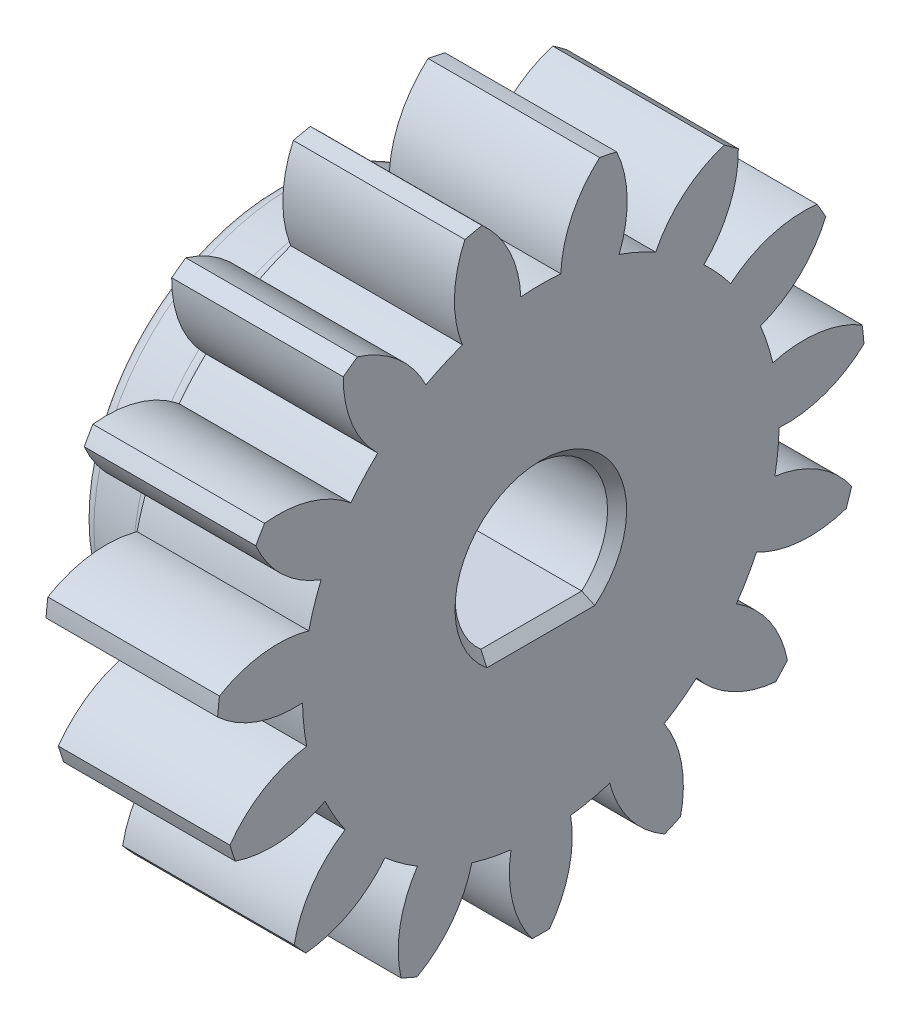
SolidWorks part; units mm, degrees
ref_plane "Plane1" through (0, 0, 0) normal (0, 0, 1) x (1, 0, 0)
ref_plane "Plane2" through (0, 0, 0) normal (0, 1, 0) x (1, 0, 0)
ref_plane "Plane3" through (0, 0, 0) normal (1, 0, 0) x (0, 0, -1)
sketch "HoldingSke" plane through (0, 0, 0) normal (0, 1, 0) x (1, 0, 0)
  line L0 (0, 0) -> (0.483, -0.1294)
  line L1 (-15, 0) -> (100, 0) construction
  line L2 (0, 0) -> (-2.1039, 2.3779)
  line L3 (0, 0) -> (-11.863, 4.5341)
  line L4 (0, 0) -> (8.3417, 2.2352)
  line L5 (0, 0) -> (-13.1173, -4.8924)
  line L6 (0, 0) -> (-7.4607, -5.0337)
  line L7 (-2.1039, 2.3779) -> (0.9096, 16.0498)
  line L8 (-76.2, 54.61) -> (-74.8, 54.61)
  line L9 (-71.009, 38.7566) -> (-53.1078, 45.2721)
  line L10 (-76.2, 71.12) -> (104.1128, 71.12)
  line L11 (0, 0) -> (-9, 0)
  line L12 (-76.2, 101.6) -> (-76.133, 101.6)
  line L13 (24.9733, 27.94) -> (52.9518, 28.4284)
  line L14 (24.9733, 27.94) -> (24.9743, 27.94)
  line L15 (24.9733, 27.94) -> (100.4006, 29.5858)
  line L16 (-63.627, -2) -> (-12.827, -2)
  circle A0 centre (0, 0) radius 4
  circle A1 centre (0, 0) radius 11
  circle A2 centre (0, 0) radius 11
  circle A3 centre (0, 0) radius 4
  dimension "Num_teeth" = 15
  dimension "Pitch_radius" = 180.3128
  dimension "Width" = 9
  dimension "Thickness" = 9
sketch "BasProSke" plane through (0, 0, 0) normal (0, 1, 0) x (1, 0, 0)
  line L0 (-10, 0) -> (60, 0) construction
  line L1 (0, 0) -> (0, 17)
  line L2 (0, 0) -> (9, 0)
  line L3 (9, 0) -> (9, 17)
  line L4 (9, 17) -> (0, 17)
  dimension "Thickness" = 9
  dimension "Diameter" = 34
revolve "Base-Revolve" add sketch "BasProSke" angle 360 about L0
sketch "TooCutSke" plane through (0, 0, 0) normal (1, 0, 0) x (0, 0, -1)
  line L1 (0, 0) -> (0, 107) construction
  line L2 (0, 0) -> (-1.6851, 14.905) construction
  line L3 (0, 0) -> (-6.2081, 29.2069) construction
  line L4 (-1.6851, 14.905) -> (-3.1041, 14.6034) construction
  arc A0 (1.0501, 12.4548) -> (-1.0501, 12.4548) centre (0, 0) ccw
  arc A1 (3.1109, 16.7388) -> (-3.1109, 16.7388) centre (0, 0) ccw
  circle A2 centre (0, 0) radius 15 construction
  circle A3 centre (0, 0) radius 14.0954 construction
  arc A4 (-1.0501, 12.4548) -> (-3.1109, 16.7388) centre (-7.045, 12.2085) ccw
  arc A5 (3.1109, 16.7388) -> (1.0501, 12.4548) centre (7.045, 12.2085) ccw
extrude "ToothCut" cut sketch "TooCutSke" along normal through all
fillet "Breaks" [suppressed] radius 0.04
fillet "RootFillets" [suppressed] radius 0.501
pattern_circular "TeethCuts" count 15 every 24 about axis through (-10, 0, 0) along (1, 0, 0) of "ToothCut", "RootFillets", "Breaks"
sketch "HubNeaOneSke" plane through (0, 0, 0) normal (-1, 0, 0) x (0, 0, 1)
  circle A0 centre (0, 0) radius 11
  dimension "Diameter" = 22
extrude "HubNearOne" add sketch "HubNeaOneSke" along normal blind 5.0001
sketch "HubNeaBotSke" plane through (0, 0, 0) normal (-1, 0, 0) x (0, 0, 1)
  circle A0 centre (0, 0) radius 11
  dimension "Diameter" = 22
extrude "HubNearBoth" [suppressed] add sketch "HubNeaBotSke" along normal blind 2.5
ref_plane "FarPln" through (9, 0, 0) normal (1, 0, 0) x (0, 0, -1)
sketch "HubFarSke" plane through (9, 0, 0) normal (1, 0, 0) x (0, 0, -1)
  circle A0 centre (0, 0) radius 11
  dimension "Diameter" = 22
extrude "HubFar" [suppressed] add sketch "HubFarSke" along normal blind 2.5
sketch "BorSke" plane through (0, 0, 0) normal (1, 0, 0) x (0, 0, -1)
  circle A0 centre (0, 0) radius 4
  dimension "Diameter" = 8
extrude "Bore" cut sketch "BorSke" along normal mid plane 28.0001
sketch "KeySke" plane through (0, 0, 0) normal (1, 0, 0) x (0, 0, -1)
  line L0 (-1.5, 0) -> (-1.5, 5.4)
  line L1 (-1.5, 5.4) -> (1.5, 5.4)
  line L2 (1.5, 5.4) -> (1.5, 0)
  line L3 (0, 0) -> (0, 34) construction
  line L4 (-1.5, 0) -> (1.5, 0)
  dimension "Width" = 3
extrude "Keyway" [suppressed] cut sketch "KeySke" along normal mid plane 28.0001
pattern_circular "Keyway2" [suppressed] count 2 every 90 about axis through (-10, 0, 0) along (1, 0, 0)
sketch "Szkic1" plane through (0, 0, 0) normal (1, 0, 0) x (0, 0, -1)
  line L0 (-4.7612, 4) -> (4.8559, 4) construction
  line L1 (-2.6458, -3) -> (2.6458, -3)
  line L2 (-2.6458, -3) -> (-2.6458, -4)
  line L3 (-2.6458, -4) -> (2.6458, -4)
  line L4 (2.6458, -3) -> (2.6458, -4)
  circle A0 centre (0, 0) radius 4 construction
  dimension "D1" = 7
extrude "Dodanie-wyciągnięcie1" add sketch "Szkic1" along normal through all and the other way through all
draft "Pochylenie1" type of draft neutral plane draft angle 10 faces to draft 1 face at (-5.0001, 0, 11) neutral plane through (0, 0, 0) neutral plane normal (-1, 0, 0) parameters "D1"=10
fillet "Zaokrąglenie1" radius 2 1 edges at (0, 0, -11)
fillet "Zaokrąglenie2" radius 1 1 edges at (-5.0001, 0, 10.1184)
chamfer "Sfazowanie1" distance 0.5 angle 45 4 edges at (-5.0001, 4, 0) (-5.0001, -3, 0) (9, -3, 0) (9, 4, 0)
equation "' \"Module@HoldingSke\" = 6.35"
equation "' \"Num_teeth@HoldingSke\" = 12"
equation "' \"Ap@HoldingSke\" =  20"
equation "' \"Ap@HoldingSke\" = 20"
equation "' \"Width@HoldingSke\" = 0.5 * 25.4"
equation "' \"Hub_dia@HoldingSke\"= 1 * 25.4"
equation "' \"Hub_dia@HoldingSke\" = 1 * 25.4"
equation "' \"Overall_len@HoldingSke\" = 1.0 * 25.4"
equation "' \"Bore@HoldingSke\" = 0.75 * 25.4"
equation "' \"T_dim@HoldingSke\" = 0.1 * 25.4"
equation "' \"Width@KeySke\" = 0.25 * 25.4"
equation "' \"Show_teeth@HoldingSke\" = 13"
equation "' \"Backlash@HoldingSke\" = 0.009 * 25.4"
equation "' \"Addendum_fac@HoldingSke\" = 1.0"
equation "' \"Dedendum_fac@HoldingSke\" = 1.25"
equation "' \"Dedendum_add@HoldingSke\" = 0.00005 * 25.4"
equation "' \"Clearance_fac@HoldingSke\" = 0.25"
equation "\"Pitch@HoldingSke\" = 1 / \"Module@HoldingSke\""
equation "\"Overcut_dia@TooCutSke\" = (\"Num_teeth@HoldingSke\" + 2 * \"Addendum_fac@HoldingSke\") / \"Pitch@HoldingSke\" + 0.002 * 25.4"
equation "\"Pitch_dia@TooCutSke\" = \"Num_teeth@HoldingSke\" / \"Pitch@HoldingSke\""
equation "\"Base_dia@TooCutSke\" = \"Num_teeth@HoldingSke\" / \"Pitch@HoldingSke\" * cos((\"Ap@HoldingSke\"  * 3.14159265 / 180))"
equation "\"Root_dia@TooCutSke\" = (\"Num_teeth@HoldingSke\" + 2) / \"Pitch@HoldingSke\" - 2 * (\"Addendum_fac@HoldingSke\" + \"Dedendum_fac@HoldingSke\") / \"Pitch@HoldingSke\" - \"Dedendum_add@HoldingSke\" * 2"
equation "\"Half_ang@TooCutSke\" = 180 / \"Num_teeth@HoldingSke\""
equation "\"Half_CT@TooCutSke\" = \"Num_teeth@HoldingSke\" / \"Pitch@HoldingSke\" * sin((3.14159265 / 2 / \"Num_teeth@HoldingSke\")) / 2 - 7 * \"Backlash@HoldingSke\" / 4"
equation "\"Flank_rad@TooCutSke\" = \"Num_teeth@HoldingSke\" / \"Pitch@HoldingSke\" / 5"
equation "\"Radius@RootFillets\" = \"Clearance_fac@HoldingSke\" / \"Pitch@HoldingSke\" + \"Dedendum_add@HoldingSke\""
equation "\"Break_rad@Breaks\" = 0.02 / \"Pitch@HoldingSke\""
equation "\"Thickness@HoldingSke\" = \"Width@HoldingSke\""
equation "\"OAL@HoldingSke\" = \"Thickness@HoldingSke\""
equation "\"MHD@HoldingSke\" = (\"Num_teeth@HoldingSke\" + 2) / \"Pitch@HoldingSke\" - 2 * (\"Addendum_fac@HoldingSke\" + \"Dedendum_fac@HoldingSke\")  / \"Pitch@HoldingSke\" - \"Dedendum_add@HoldingSke\" * 2"
equation "\"MBD@HoldingSke\" = (\"Num_teeth@HoldingSke\" + 2) / \"Pitch@HoldingSke\" - 2 * (\"Addendum_fac@HoldingSke\" + \"Dedendum_fac@HoldingSke\")  / \"Pitch@HoldingSke\" - \"Dedendum_add@HoldingSke\" * 2 - 0.002 * 25.4"
equation "\"MHD@HoldingSke\" = ((sgn( \"MHD@HoldingSke\" - \"Hub_dia@HoldingSke\" )-1)*( \"MHD@HoldingSke\" - \"Hub_dia@HoldingSke\" ))/-2+ \"Hub_dia@HoldingSke\""
equation "\"MBD@HoldingSke\" = ((sgn( \"MBD@HoldingSke\" - \"Bore@HoldingSke\" )-1)*( \"MBD@HoldingSke\" - \"Bore@HoldingSke\" ))/-2+ \"Bore@HoldingSke\""
equation "\"OAL@HoldingSke\" = ((sgn( \"OAL@HoldingSke\" - \"Overall_len@HoldingSke\" )+1)*( \"OAL@HoldingSke\" - \"Overall_len@HoldingSke\" ))/2 + \"Overall_len@HoldingSke\" + 0.000002 * 25.4"
equation "\"Num_teeth@TeethCuts\" = int( \"Show_teeth@HoldingSke\" ) + 1"
equation "\"Num_teeth@TeethCuts\" = ((sgn( \"Num_teeth@TeethCuts\" - \"Num_teeth@HoldingSke\" )-1)*( \"Num_teeth@TeethCuts\" - \"Num_teeth@HoldingSke\" ))/-2+ \"Num_teeth@HoldingSke\""
equation "\"Num_teeth@TeethCuts\" = ((sgn( \"Num_teeth@TeethCuts\" - 2.0)+1)*( \"Num_teeth@TeethCuts\" - 2.0))/2 +2.0"
equation "\"Angle@TeethCuts\" = 360.0 / \"Num_teeth@HoldingSke\""
equation "\"Diameter@BasProSke\" = (\"Num_teeth@HoldingSke\" + 2 * \"Addendum_fac@HoldingSke\") / \"Pitch@HoldingSke\""
equation "\"Thickness@BasProSke\"  = \"Thickness@HoldingSke\""
equation "' \"Fillet_rad@BasProSke\" =  \"Thickness@HoldingSke\" * 0.05"
equation "' \"Fillet_rad@BasProSke\" = \"Thickness@HoldingSke\" * 0.05"
equation "\"MHD@HoldingSke\" = ((sgn( \"MHD@HoldingSke\" - \"Root_dia@TooCutSke\" )-1)*( \"MHD@HoldingSke\" - \"Root_dia@TooCutSke\" ))/-2+ \"Root_dia@TooCutSke\""
equation "\"Diameter@HubNeaOneSke\" = \"MHD@HoldingSke\""
equation "\"Length@HubNearOne\" = \"OAL@HoldingSke\" - \"Thickness@BasProSke\""
equation "\"Diameter@HubNeaBotSke\" = \"MHD@HoldingSke\""
equation "\"Length@HubNearBoth\" = ( \"OAL@HoldingSke\" - \"Thickness@BasProSke\" ) / 2.0"
equation "\"Thickness@FarPln\" = \"Thickness@BasProSke\""
equation "\"Diameter@HubFarSke\" = \"MHD@HoldingSke\""
equation "\"Length@HubFar\" = ( \"OAL@HoldingSke\" - \"Thickness@BasProSke\" ) / 2.0"
equation "\"Diameter@BorSke\" = \"MBD@HoldingSke\""
equation "\"D1@Bore\" = \"OAL@HoldingSke\" * 2.0"
equation "\"D1@Keyway\" = \"OAL@HoldingSke\" * 2.0"
equation "\"Offset@KeySke\" = \"T_dim@HoldingSke\" + \"MBD@HoldingSke\" / 2.0"
